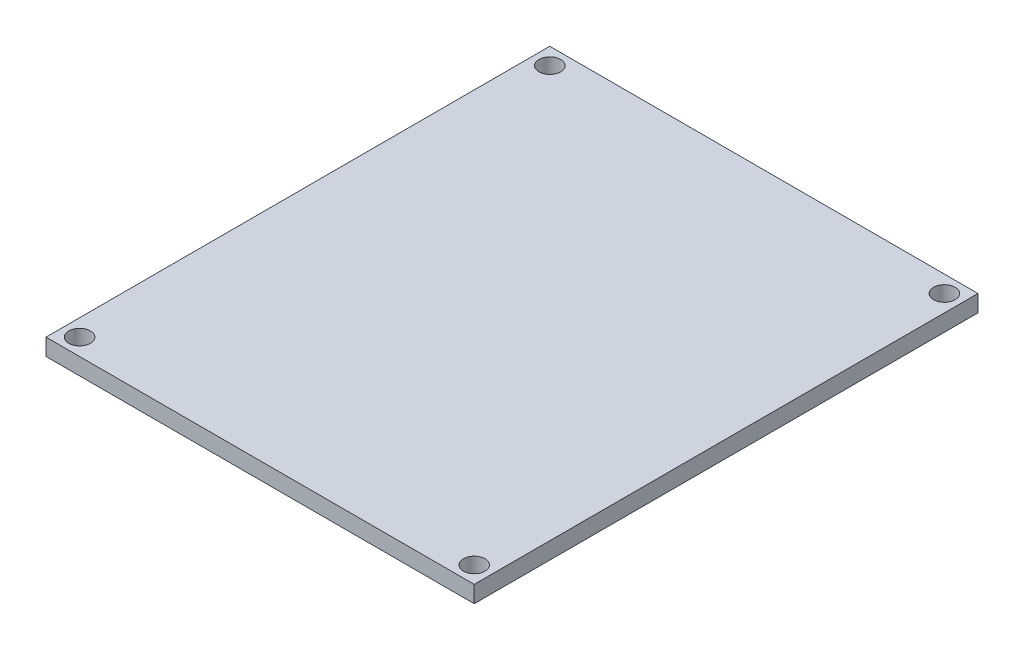
SolidWorks part; units mm, degrees
ref_plane "Front Plane" through (0, 0, 0) normal (0, 0, 1) x (1, 0, 0)
ref_plane "Top Plane" through (0, 0, 0) normal (0, 1, 0) x (1, 0, 0)
ref_plane "Right Plane" through (0, 0, 0) normal (1, 0, 0) x (0, 0, -1)
sketch "Sketch1" plane through (0, 0, 0) normal (0, 1, 0) x (1, 0, 0)
  line L1 (0, 0) -> (64.77, 0)
  line L2 (0, 0) -> (0, 76.2)
  line L3 (0, 76.2) -> (64.77, 76.2)
  line L4 (64.77, 0) -> (64.77, 76.2)
  dimension "D1" = 64.77
  dimension "D2" = 76.2
extrude "Boss-Extrude1" add sketch "Sketch1" along normal blind 2.54
hole_wizard "#4 Clearance Hole1" positions "Sketch3" profile "Sketch2" hole size "#4" standard "ANSI Inch"
sketch "Sketch3" plane through (0, 2.54, 0) normal (0, 1, 0) x (1, 0, 0)
  line L0 (0, 76.2) -> (0, 0) construction
  line L1 (64.77, 76.2) -> (0, 76.2) construction
  line L2 (64.77, 0) -> (64.77, 76.2) construction
  line L3 (0, 0) -> (64.77, 0) construction
  point P0 (2.54, 73.66)
  point P2 (2.54, 2.54)
  point P4 (62.23, 73.66)
  point P6 (62.23, 2.54)
  dimension "D1" = 2.54
  dimension "D2" = 2.54
  dimension "D3" = 2.54
  dimension "D4" = 2.54
sketch "Sketch2" plane through (2.54, 2.54, -73.66) normal (1, 0, 0) x (0, 0, 1)
  line L0 (0, 0) -> (0, 11.1406)
  line L1 (0, 11.1406) -> (1.6319, 10.16)
  line L2 (1.6319, 10.16) -> (1.6319, 0)
  line L5 (1.6319, 0) -> (0, 0)
  line L10 (0, 11.1406) -> (-1.6319, 10.16) construction
  line L11 (0, -6.35) -> (0, 107.95) construction
  dimension "Hole Dia." = 3.2639
  dimension "Hole Depth" = 10.16
  dimension "Drill Angle" = 118
